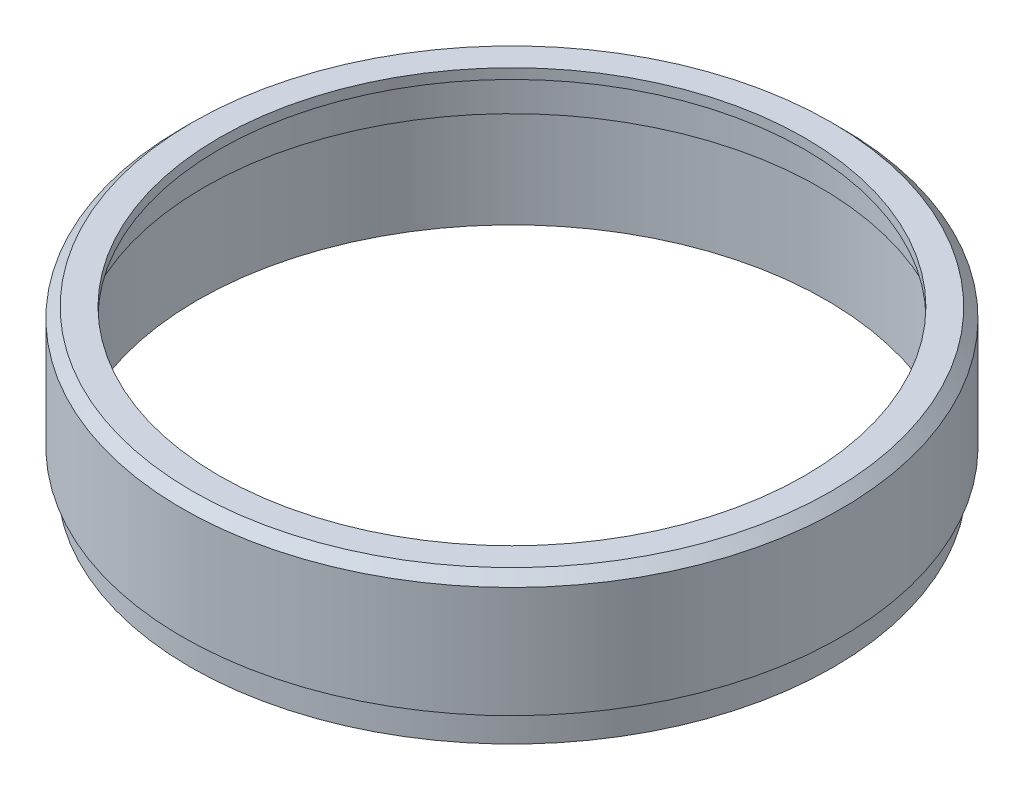
SolidWorks part; units mm, degrees
ref_plane "Front Plane" through (0, 0, 0) normal (0, 0, 1) x (1, 0, 0)
ref_plane "Top Plane" through (0, 0, 0) normal (0, 1, 0) x (1, 0, 0)
ref_plane "Right Plane" through (0, 0, 0) normal (1, 0, 0) x (0, 0, -1)
ref_axis "Axis1" through (0, 0, 0) along (0, 1, 0)
sketch "Sketch1" plane through (0, 0, 0) normal (0, 0, 1) x (1, 0, 0)
  line L0 (0, 0) -> (0, -50000) construction
  line L1 (-32.65, 4) -> (-31.85, 4)
  line L2 (31.9, 4) -> (-31.9, 4) construction
  line L3 (-31.85, 4) -> (-31.85, 1)
  line L4 (31.9, 1) -> (-31.9, 1) construction
  line L5 (-31.85, 1) -> (-31.15, 1)
  line L6 (-31.15, 1) -> (-31.15, 11)
  line L7 (-31.9, 4) -> (-31.9, 1) construction
  line L8 (-32.65, 4) -> (-32.65, 15)
  line L9 (-31.15, 11) -> (-30.5, 11)
  line L10 (-30.5, 11) -> (-30.5, 15)
  line L11 (-30.5, 15) -> (-29, 15)
  line L15 (-29, 15) -> (-29, 16)
  line L24 (-29, 16) -> (-31.65, 16)
  line L25 (-31.65, 16) -> (-32.65, 15)
  line L27 (-30.5, 11) -> (30.5, 11) construction
  dimension "D1" = 0.05
  dimension "D2" = 30.5
  dimension "D3" = 1.5
  dimension "D4" = 4
  dimension "D5" = 1.5
  dimension "D6" = 1
  dimension "D7" = 1
  dimension "D10" = 135
revolve "Revolve1" add sketch "Sketch1" angle 360 about L0
